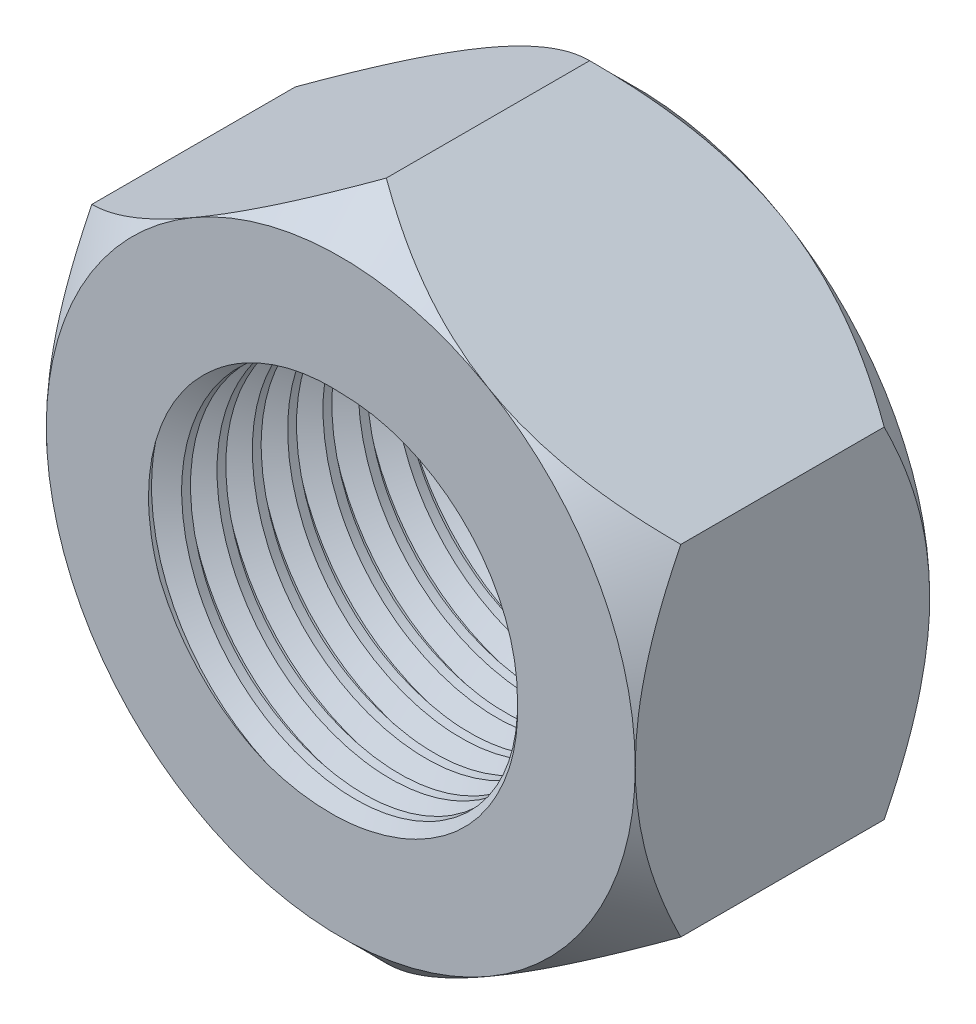
SolidWorks part; units mm, degrees
material "Cast Stainless Steel"
ref_plane "Front Plane" through (0, 0, 0) normal (0, 0, 1) x (1, 0, 0)
ref_plane "Top Plane" through (0, 0, 0) normal (0, 1, 0) x (1, 0, 0)
ref_plane "Right Plane" through (0, 0, 0) normal (1, 0, 0) x (0, 0, -1)
sketch "Sketch1" plane through (0, 0, 0) normal (0, 0, 1) x (1, 0, 0)
  line L0 (0, 0) -> (0, 13.0402) construction
  line L1 (0, 7.698) -> (-6.6667, 3.849)
  line L2 (-6.6667, 3.849) -> (-6.6667, -3.849)
  line L3 (-6.6667, -3.849) -> (0, -7.698)
  line L4 (0, -7.698) -> (6.6667, -3.849)
  line L5 (6.6667, -3.849) -> (6.6667, 3.849)
  line L6 (6.6667, 3.849) -> (0, 7.698)
  circle A0 centre (0, 0) radius 6.6667 construction
  dimension "D1" = 13.3333
extrude "Boss-Extrude1" add sketch "Sketch1" along normal mid plane 6.6667
sketch "Sketch2" plane through (0, 0, 3.3333) normal (0, 0, 1) x (1, 0, 0)
  circle A0 centre (0, 0) radius 4
  dimension "D1" = 8
sketch "Sketch11" plane through (0, 0, 3.3333) normal (0, 0, 1) x (1, 0, 0)
  circle A0 centre (0, 0) radius 6.6667
  dimension "D1" = 13.3333
extrude "Cut-Extrude5" cut sketch "Sketch11" against normal blind 50 draft 45 flip side to cut
mirror "Mirror1" about plane through (0, 0, 0) normal (0, 0, 1) of "Cut-Extrude5"
extrude "Cut-Extrude6" cut sketch "Sketch2" against normal up to next
thread "Thread3" pitch 0.8 profile "Thread Profile3" start angle 0, offset 5, length 51, pitch 0.8, diameter 8
ref_plane "Plane3" through (-4, 0, 8.3333) normal (0, -1, 0) x (-1, 0, 0)
sketch "Thread Profile3" plane through (-4, 0, 8.3333) normal (0, -1, 0) x (-1, 0, 0)
  line L0 (0, 0) -> (0, 0.8) construction
  line L1 (0, 0) -> (0.433, 0.25)
  line L2 (0.433, 0.25) -> (0.433, 0.35)
  line L3 (0.433, 0.35) -> (0, 0.6)
  line L4 (0.433, 0.3) -> (0, 0.3) construction
  line L11 (0, 0) -> (0, 0.6)
  point P2 (0, 0)
  dimension "Pitch" = 0.8
  dimension "Profile_Angle" = 60
  dimension "Profile_Land" = 0.1
  dimension "Profile_Height" = 0.433
